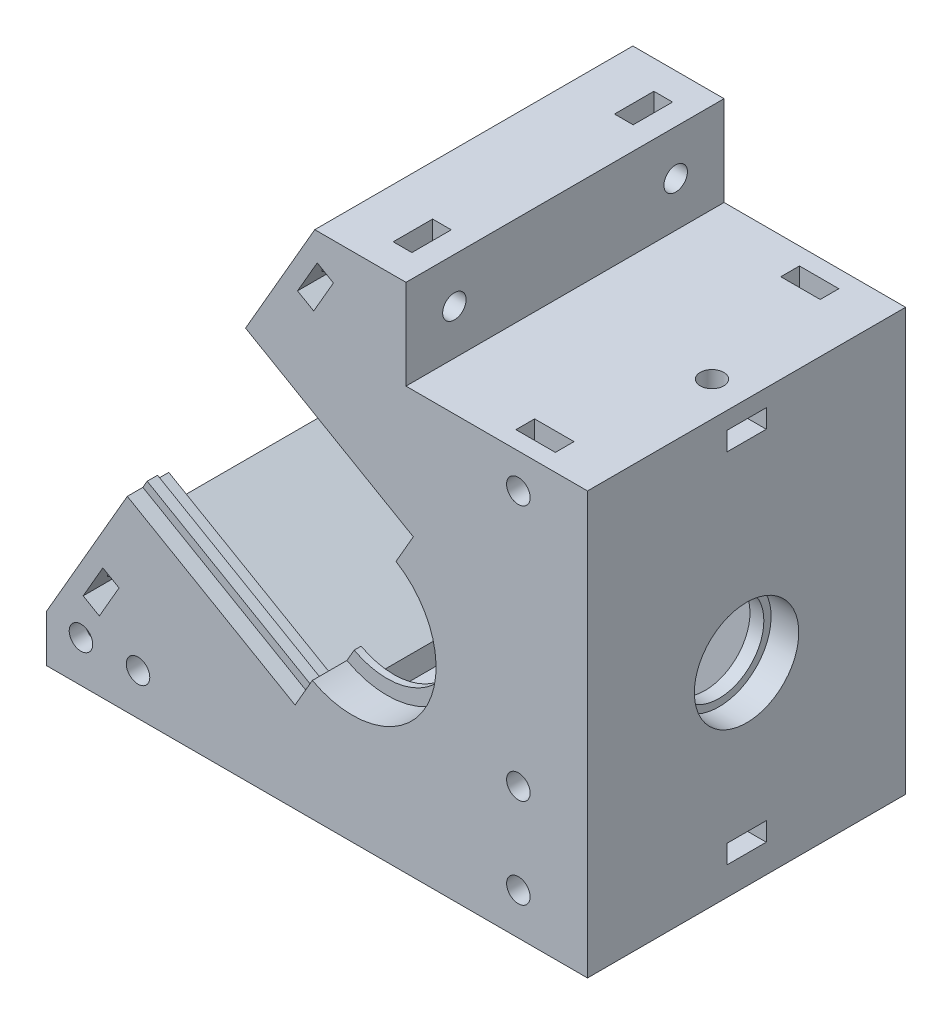
SolidWorks part; units mm, degrees
material "ABS"
ref_plane "Front Plane" through (0, 0, 0) normal (0, 0, 1) x (1, 0, 0)
ref_plane "Top Plane" through (0, 0, 0) normal (0, 1, 0) x (1, 0, 0)
ref_plane "Right Plane" through (0, 0, 0) normal (1, 0, 0) x (0, 0, -1)
sketch "Sketch1" plane through (0, 0, 0) normal (0, 0, 1) x (1, 0, 0)
  line L0 (-14, -24.2487) -> (-38, -10.3923)
  line L1 (-38, 33) -> (34, 33)
  line L2 (-38, 33) -> (-38, -31)
  line L3 (-38, -31) -> (34, -31)
  line L4 (34, 33) -> (34, -31)
  line L7 (-15, -31) -> (-15, -27.5)
  line L8 (-15, -27.5) -> (15, -27.5)
  line L9 (15, -27.5) -> (15, -31)
  line L16 (14, 24.2487) -> (-10, 38.1051)
  line L17 (7.75, 33) -> (7.75, 46)
  line L18 (7.75, 46) -> (-5.25, 46)
  line L19 (28, 10) -> (28, -10)
  line L20 (28, 10) -> (28, 14)
  line L21 (28, 14) -> (16.8, 22.4)
  line L22 (-38, -10.3923) -> (-5.4419, 46)
  line L23 (-5.4419, 46) -> (-5.25, 46)
  line L24 (-38, -10.3923) -> (-44.25, -21.2176)
  line L25 (-44.25, -21.2176) -> (-44.25, -31)
  line L26 (-44.25, -31) -> (-38, -31)
  line L27 (-44.25, -21.2176) -> (-44.25, -15.2176) construction
  line L28 (-44.25, -15.2176) -> (-8.906, 46) construction
  line L29 (-8.906, 46) -> (-5.4419, 46) construction
  line L30 (-10, 38.1051) -> (-12.5981, 39.6051) construction
  line L31 (-38, -10.3923) -> (-40.5981, -8.8923) construction
  line L32 (28, -10) -> (28, -14)
  line L33 (28, -14) -> (16.8, -22.4)
  circle A0 centre (0, 0) radius 28
  circle A1 centre (0, 0) radius 12.1
  circle A2 centre (0, 0) radius 10
  point P22 (28, 0)
  dimension "D1" = 56
  dimension "D2" = 24.2
  dimension "D3" = 20
  dimension "D4" = 34
  dimension "D6" = 3.5
  dimension "D7" = 15
  dimension "D8" = 15
  dimension "D10" = 38
  dimension "D5" = 33
  dimension "D9" = 31
  dimension "D11" = 30
  dimension "D12" = 7.75
  dimension "D13" = 13
  dimension "D14" = 13
  dimension "D15" = 20
  dimension "D16" = 9.1162
  dimension "D17" = 12.5
  dimension "D18" = 3
  dimension "D19" = 7.3038
  dimension "D20" = 7.3842
  dimension "D21" = 4
  dimension "D22" = 4
extrude "Boss-Extrude1" add sketch "Sketch1" along normal blind 6 contours A0 L20 L19 L8 L9 L3 L4 L1 L16 | A0 L0 L2 L3 L7 L8 | L25 L26 L2 L24 | L23 L22 L16 L1 L17 L18 | A0 L22 L0 | L22 A0 L8 A1 | A0 L16 L1 L22 | L22 L1 L16 | A0 L19 L20 | A0 L19 region at (-27.5845, -23.6186, 0) region at (-29.6112, -8.3492, 0) region at (-25.7125, -8.9071, 0) region at (-40.7539, -23.0811, 0) region at (-7.4692, 28.6958, 0) region at (11.6201, -26.2754, 0) region at (-8.035, 34.7017, 0) region at (25.6746, -12.8373, 0) region at (0.2743, 39.7035, 0) region at (25.6746, 12.8373, 0)
extrude "Boss-Extrude2" add sketch "Sketch1<3>" along normal blind 40 contours A0 L20 L19 L8 L9 L3 L4 L1 L16 | L23 L22 L16 L1 L17 L18 | A0 L0 L2 L3 L7 L8 | L25 L26 L2 L24 region at (-27.5845, -23.6186, 0) region at (-40.7539, -23.0811, 0) region at (11.6201, -26.2754, 0) region at (0.2743, 39.7035, 0)
sketch "Sketch1<3>" plane through (0, 0, 0) normal (0, 0, 1) x (1, 0, 0) same geometry as "Sketch1"
extrude "Boss-Extrude3" add sketch "Sketch1<4>" along normal blind 6 from surface contours A0 L20 L19 L8 L9 L3 L4 L1 L16 | L22 A0 L8 A1 | A0 L19 L20 | A0 L19 | A0 L0 L2 L3 L7 L8 | A0 L22 L0 | A0 L16 L1 L22 | L22 L1 L16 | L23 L22 L16 L1 L17 L18 | L25 L26 L2 L24 region at (-27.5845, -23.6186, 0) region at (-29.6112, -8.3492, 0) region at (-25.7125, -8.9071, 0) region at (-40.7539, -23.0811, 0) region at (-7.4692, 28.6958, 0) region at (11.6201, -26.2754, 0) region at (-8.035, 34.7017, 0) region at (25.6746, -12.8373, 0) region at (0.2743, 39.7035, 0) region at (25.6746, 12.8373, 0) starting at face at (14.8032, 7.3384, 40)
sketch "Sketch1<4>" plane through (0, 0, 0) normal (0, 0, 1) x (1, 0, 0) same geometry as "Sketch1"
extrude "Boss-Extrude4" add sketch "Sketch1<5>" against normal blind 1 from surface contours A1 A2 region at (-11.7578, 0, 0) starting at face at (4.1782, -2.8269, 6)
sketch "Sketch1<5>" plane through (0, 0, 0) normal (0, 0, 1) x (1, 0, 0) same geometry as "Sketch1"
extrude "Boss-Extrude5" add sketch "Sketch1<6>" along normal blind 1 from surface contours A1 A2 region at (-11.7578, 0, 0) starting at face at (4.1782, -2.8269, 40)
sketch "Sketch1<6>" plane through (0, 0, 0) normal (0, 0, 1) x (1, 0, 0) same geometry as "Sketch1"
sketch "Sketch2" plane through (0, -27.5, 0) normal (0, -1, 0) x (1, 0, 0)
  line L0 (15, 46) -> (15, 0) construction
  line L1 (15, 40) -> (-15, 40)
  line L2 (15, 40) -> (15, 6)
  line L3 (15, 6) -> (-15, 6)
  line L4 (-15, 40) -> (-15, 6)
  line L5 (-15, 46) -> (-15, 0) construction
  line L6 (-5.2678, 6) -> (5.2678, 6) construction
  line L7 (5.2678, 40) -> (-5.2678, 40) construction
sketch "Sketch3" plane through (0, 0, 0) normal (0, 0, -1) x (-1, 0, 0)
  line L0 (-6.05, 10.4789) -> (17.95, 24.3353)
  line L1 (44.25, -21.2176) -> (5.4419, 46) construction
  line L2 (6.05, -10.4789) -> (30.05, 3.3775)
  line L3 (-8.55, 14.809) -> (15.45, 28.6654)
  line L4 (8.2902, -14.959) -> (32.55, -0.9526)
  line L5 (6.05, -10.4789) -> (30.05, 3.3775) construction
  line L6 (-8.55, 14.809) -> (-6.05, 10.4789)
  line L7 (8.55, -14.809) -> (6.05, -10.4789)
  line L8 (-6.05, 10.4789) -> (6.05, -10.4789)
  line L9 (-8.55, 14.809) -> (-8.8098, 14.659)
  line L10 (-8.8098, 14.659) -> (8.2902, -14.959)
  line L11 (8.55, -14.809) -> (32.55, -0.9526) construction
  circle A0 centre (0, 0) radius 12.1 construction
  line M11 (44.25, -21.2176) -> (5.4419, 46)
  circle M17 centre (0, 0) radius 12.1
  dimension "D1" = 90
  dimension "D2" = 90
  dimension "D5" = 90
  dimension "D6" = 0.3
  dimension "D7" = 27.7128
  dimension "D3" = 5
  dimension "D4" = 5
extrude "Cut-Extrude1" cut sketch "Sketch2" against normal blind 10
extrude "Cut-Extrude2" cut sketch "Sketch3" against normal blind 49 contours L3 L6 L0 M11 | L2 L0 M17 M11 | L8 M17 | L9 L10 L6 M17 | L10 L8 M17 | L7 L4 L2 M11 | L10 L4 L7 M17 region at (-4.7, 19.5722, 0) region at (7.4296, 12.5684, 0) region at (-4.4474, 2.5677, 0) region at (-15.9416, 9.2039, 0) region at (0.1299, -0.075, 0) region at (-19.3, -5.7158, 0) region at (-7.1698, -12.7184, 0)
sketch "Sketch4" plane through (0.2598, -0.15, 0) normal (-0.866, 0.5, 0) x (0, 0, 1)
  line L0 (6, 17.1) -> (0, 17.1) construction
  line L1 (2.25, 17.1) -> (3.75, 17.1)
  line L2 (2.25, 17.1) -> (2.25, 15.85)
  line L3 (2.25, 15.85) -> (3.75, 15.85)
  line L4 (3.75, 17.1) -> (3.75, 15.85)
  line L5 (42.25, 17.1) -> (43.75, 17.1)
  line L6 (42.25, 17.1) -> (42.25, 15.85)
  line L7 (42.25, 15.85) -> (43.75, 15.85)
  line L8 (43.75, 17.1) -> (43.75, 15.85)
  line L9 (46, 17.1) -> (40, 17.1) construction
  line L10 (2.25, -15.85) -> (3.75, -15.85)
  line L11 (2.25, -15.85) -> (2.25, -17.1)
  line L12 (2.25, -17.1) -> (3.75, -17.1)
  line L13 (3.75, -15.85) -> (3.75, -17.1)
  line L14 (42.25, -15.85) -> (43.75, -15.85)
  line L15 (42.25, -15.85) -> (42.25, -17.1)
  line L16 (42.25, -17.1) -> (43.75, -17.1)
  line L17 (43.75, -15.85) -> (43.75, -17.1)
  line L18 (6, -17.1) -> (0, -17.1) construction
  line L19 (46, -17.1) -> (40, -17.1) construction
  point P6 (3, 17.1)
  point P7 (3, 17.1)
  point P12 (43, 17.1)
  point P15 (43, 17.1)
  point P28 (3, -17.1)
  point P29 (3, -17.1)
  point P30 (43, -17.1)
  point P33 (43, -17.1)
  dimension "D1" = 1.5
  dimension "D2" = 1.25
  dimension "D3" = 1.5
  dimension "D4" = 1.25
  dimension "D5" = 1.5
  dimension "D6" = 1.25
  dimension "D7" = 1.5
  dimension "D8" = 1.25
extrude "Boss-Extrude6" add sketch "Sketch4" along normal up to surface (28.0128 mm away) up to face at (-11.5855, 35.359, 23)
sketch "Sketch5" plane through (28, 0, 0) normal (-1, 0, 0) x (0, 0, 1)
  line L0 (40, 14) -> (6, -14) construction
  circle A0 centre (23, 0) radius 7.55
  circle A1 centre (23, 0) radius 6.5
  point P7 (23, 0)
  dimension "D1" = 15.1
  dimension "D2" = 13
extrude "Cut-Extrude3" cut sketch "Sketch5" against normal blind 49 contours A1 L0 | L0 A1 region at (28, -2.1295, 24.7537) region at (28, 2.1295, 21.2463)
extrude "Cut-Extrude4" cut sketch "Sketch5<3>" along normal blind 4 from surface contours L0 A0 A1 | A0 L0 A1 region at (28, 2.4881, 29.9351) region at (28, 4.6064, 28.3071) starting at face at (34, 6.5, 23)
sketch "Sketch5<3>" plane through (28, 0, 0) normal (-1, 0, 0) x (0, 0, 1) same geometry as "Sketch5"
sketch "Sketch6" plane through (-24, 13.8564, 0) normal (-0.866, 0.5, 0) x (0, 0, 1)
  line L0 (40, -28) -> (6, -28) construction
  line L1 (0, -40.5) -> (0, -17.1) construction
  line L2 (46, -17.1) -> (46, -40.5) construction
  line L3 (40, 28) -> (6, 28) construction
  line L5 (46, -40.5) -> (0, -40.5) construction
  circle A0 centre (4, -31) radius 1.7
  circle A1 centre (42, -31) radius 1.7
  circle A2 centre (42, 31) radius 1.7
  circle A3 centre (4, 31) radius 1.7
  dimension "D1" = 3.4
  dimension "D2" = 3.4
  dimension "D3" = 3.4
  dimension "D4" = 3.4
  dimension "D5" = 3
  dimension "D6" = 4
  dimension "D7" = 4
  dimension "D8" = 3
  dimension "D9" = 9.5
  dimension "D10" = 62
  dimension "D11" = 38
extrude "Cut-Extrude5" cut sketch "Sketch6" against normal blind 8
sketch "Sketch7" plane through (0, 0, 46) normal (0, 0, 1) x (1, 0, 0)
  line L0 (34, -31) -> (34, 33) construction
  line L1 (-44.25, -31) -> (34, -31)
  line L2 (-44.25, -31) -> (-44.25, -27)
  line L3 (-44.25, -27) -> (34, -27)
  line L4 (34, -31) -> (34, -27)
  line L6 (15, -27.5) -> (-15, -27.5) construction
  dimension "D1" = 0.5
extrude "Cut-Extrude6" cut sketch "Sketch7" against normal blind 64
sketch "Sketch8" plane through (0, 0, 46) normal (0, 0, 1) x (1, 0, 0)
  line L0 (34, -27) -> (-44.25, -27) construction
  line L1 (-44.25, -27) -> (-44.25, -21.2176) construction
  line L2 (34, -27) -> (34, 33) construction
  circle A0 centre (-39.25, -22) radius 1.7
  circle A1 centre (29, -22) radius 1.7
  dimension "D1" = 3.4
  dimension "D2" = 3.4
  dimension "D3" = 5
  dimension "D4" = 5
  dimension "D5" = 5
  dimension "D6" = 5
extrude "Cut-Extrude7" cut sketch "Sketch8" against normal blind 10 contours A0 region at (-39.25, -22, 46)
extrude "Cut-Extrude9" cut sketch "Sketch8<2>" along normal blind 10 from surface contours A0 region at (-39.25, -22, 46) starting at face at (-3.6295, 7.9996, 0)
sketch "Sketch8<2>" plane through (0, 0, 46) normal (0, 0, 1) x (1, 0, 0) same geometry as "Sketch8"
sketch "Sketch10" plane through (-44.25, 0, 0) normal (-1, 0, 0) x (0, 0, 1)
  line L0 (0, -27) -> (46, -27) construction
  line L1 (20.15, -21.2176) -> (25.85, -21.2176)
  line L2 (20.15, -21.2176) -> (20.15, -23.9176)
  line L3 (20.15, -23.9176) -> (25.85, -23.9176)
  line L4 (25.85, -21.2176) -> (25.85, -23.9176)
  line L5 (20.15, -21.2176) -> (25.85, -23.9176) construction
  line L6 (20.15, -23.9176) -> (25.85, -21.2176) construction
  line L7 (46, -21.2176) -> (0, -21.2176) construction
  point P0 (23, -22.5676)
  point P8 (23, -27)
  dimension "D1" = 5.7
  dimension "D2" = 2.7
extrude "Cut-Extrude10" cut sketch "Sketch10" against normal blind 8.5
sketch "Sketch11" plane through (34, 0, 0) normal (1, 0, 0) x (0, 0, -1)
  line L0 (0, -27) -> (-46, -27) construction
  line L1 (-43.7, -24.85) -> (-41, -24.85)
  line L2 (-43.7, -24.85) -> (-43.7, -19.15)
  line L3 (-43.7, -19.15) -> (-41, -19.15)
  line L4 (-41, -24.85) -> (-41, -19.15)
  line L5 (-43.7, -24.85) -> (-41, -19.15) construction
  line L6 (-43.7, -19.15) -> (-41, -24.85) construction
  line L7 (-46, -27) -> (-46, 33) construction
  line L8 (-5, -24.85) -> (-2.5, -24.85)
  line L9 (-5, -24.85) -> (-5, -19.15)
  line L10 (-5, -19.15) -> (-2.5, -19.15)
  line L11 (-2.5, -24.85) -> (-2.5, -19.15)
  line L12 (-5, -24.85) -> (-2.5, -19.15) construction
  line L13 (-5, -19.15) -> (-2.5, -24.85) construction
  line L14 (0, 33) -> (0, -27) construction
  point P0 (-42.35, -22)
  point P9 (-3.75, -22)
  dimension "D1" = 5.7
  dimension "D2" = 2.7
  dimension "D3" = 5
  dimension "D4" = 5
  dimension "D5" = 5.7
  dimension "D6" = 2.5
  dimension "D7" = 5
extrude "Cut-Extrude12" cut sketch "Sketch11" along normal blind 8.5 from surface starting at face at (-44.25, -23.3382, 23)
extrude "Cut-Extrude13" cut sketch "Sketch10<2>" along normal blind 8.5 from surface starting at face at (34, 3, 23)
sketch "Sketch10<2>" plane through (-44.25, 0, 0) normal (-1, 0, 0) x (0, 0, 1) same geometry as "Sketch10"
sketch "Sketch12" plane through (0, 0, 46) normal (0, 0, 1) x (1, 0, 0)
  line L0 (-36.0831, -11.6722) -> (-38.9331, -16.6086)
  line L1 (-38.9331, -16.6086) -> (-36.5949, -17.9586)
  line L2 (-36.5949, -17.9586) -> (-33.7449, -13.0222)
  line L3 (-33.7449, -13.0222) -> (-36.0831, -11.6722)
  line L4 (-32.55, -0.9526) -> (-44.25, -21.2176) construction
  line L6 (-39.5, -12.9904) -> (-28.0908, -19.5775) construction
  line L7 (-5.0831, 42.0214) -> (-7.9331, 37.085)
  line L8 (-7.9331, 37.085) -> (-5.5949, 35.735)
  line L9 (-5.5949, 35.735) -> (-2.7449, 40.6714)
  line L10 (-2.7449, 40.6714) -> (-5.0831, 42.0214)
  point P6 (-37.5081, -14.1404)
  point P7 (-39.5, -12.9904)
  point P17 (-8.7952, 39.4691)
  dimension "D1" = 2.7
  dimension "D2" = 5.7
  dimension "D3" = 5
  dimension "D4" = 9.5
  dimension "D5" = 90
  dimension "D6" = 2.7
  dimension "D7" = 5.7
  dimension "D8" = 62
extrude "Cut-Extrude14" cut sketch "Sketch12" against normal blind 7.5
extrude "Cut-Extrude15" cut sketch "Sketch12<2>" along normal blind 7.5 from surface starting at face at (-37.55, -22, 0)
sketch "Sketch12<2>" plane through (0, 0, 46) normal (0, 0, 1) x (1, 0, 0) same geometry as "Sketch12"
sketch "Sketch13" plane through (7.75, 0, 0) normal (1, 0, 0) x (0, 0, -1)
  line L0 (-46, 46) -> (0, 46) construction
  line L1 (-46, 46) -> (0, 33) construction
  circle A0 centre (-39, 39.5) radius 1.7
  circle A1 centre (-7, 39.5) radius 1.7
  point P10 (-23, 39.5)
  dimension "D1" = 3.4
  dimension "D2" = 3.4
  dimension "D3" = 6.5
  dimension "D4" = 16
  dimension "D5" = 16
extrude "Cut-Extrude16" cut sketch "Sketch13" against normal blind 10
sketch "Sketch14" plane through (0, 46, 0) normal (0, 1, 0) x (1, 0, 0)
  line L0 (1.75, -9.85) -> (4.45, -9.85)
  line L1 (1.75, -41.85) -> (4.45, -41.85)
  line L2 (1.75, -41.85) -> (1.75, -36.15)
  line L3 (1.75, -36.15) -> (4.45, -36.15)
  line L4 (4.45, -41.85) -> (4.45, -36.15)
  line L5 (1.75, -41.85) -> (4.45, -36.15) construction
  line L6 (1.75, -36.15) -> (4.45, -41.85) construction
  line L7 (1.75, -9.85) -> (1.75, -4.15)
  line L8 (1.75, -4.15) -> (4.45, -4.15)
  line L9 (4.45, -9.85) -> (4.45, -4.15)
  line L10 (1.75, -9.85) -> (4.45, -4.15) construction
  line L11 (1.75, -4.15) -> (4.45, -9.85) construction
  line L12 (7.75, -46) -> (7.75, 0) construction
  point P0 (3.1, -39)
  point P5 (3.1, -7)
  point P13 (7.75, -23)
  dimension "D1" = 2.7
  dimension "D2" = 5.7
  dimension "D3" = 2.7
  dimension "D4" = 5.7
  dimension "D5" = 6
  dimension "D6" = 16
  dimension "D7" = 16
extrude "Cut-Extrude17" cut sketch "Sketch14" against normal blind 10
sketch "Sketch15" plane through (0, 0, 46) normal (0, 0, 1) x (1, 0, 0)
  line L0 (0, 30.9475) -> (0, -37.7326) construction
  line L1 (0, 0) -> (-6.3411, -23.6652) construction
  line L2 (34, -27) -> (-44.25, -27) construction
  line L3 (0, 0) -> (6.3411, 23.6652) construction
  line L4 (34, 33) -> (7.75, 33) construction
  line L5 (-6.3411, -23.6652) -> (-16.7248, -20.8829) construction
  line L6 (-6.3411, -23.6652) -> (4.0426, -26.4475) construction
  line L7 (-16.7248, -20.8829) -> (-24.6937, -18.7476) construction
  line L8 (-24.6937, -18.7476) -> (-2.694, 63.3561) construction
  dimension "D1" = 15
  dimension "D2" = 24.5
  dimension "D3" = 44.25
  dimension "D4" = 34
  dimension "D5" = 27
  dimension "D6" = 15
  dimension "D7" = 24.5
  dimension "D8" = 1.4089
  dimension "D9" = 9.3348
  dimension "D10" = 40.3411
  dimension "D11" = 3.3348
  dimension "D12" = 10.75
  dimension "D13" = 10.75
  dimension "D14" = 8.25
  dimension "D15" = 85
  dimension "D16" = 17.3561
  dimension "D17" = 10.444
  dimension "D18" = 14.5802
sketch "Sketch17" plane through (0, 0, 46) normal (0, 0, 1) x (1, 0, 0)
  line L0 (34, -27) -> (-44.25, -27) construction
  circle A0 centre (-31, -22) radius 1.7
  circle A1 centre (24, -22) radius 1.7
  dimension "D2" = 3.4
  dimension "D3" = 3.4
  dimension "D1" = 5
  dimension "D4" = 31
  dimension "D5" = 24
extrude "Cut-Extrude19" cut sketch "Sketch17" against normal blind 20
extrude "Cut-Extrude20" cut sketch "Sketch17<2>" along normal blind 20 from surface starting at face at (-5.339, 38.8782, 0)
sketch "Sketch17<2>" plane through (0, 0, 46) normal (0, 0, 1) x (1, 0, 0) same geometry as "Sketch17"
sketch "Sketch19" plane through (0, -27, 0) normal (0, -1, 0) x (1, 0, 0)
  line L1 (-44.25, 46) -> (34, 46)
  line L2 (-44.25, 46) -> (-44.25, 0)
  line L3 (-44.25, 0) -> (34, 0)
  line L4 (34, 46) -> (34, 0)
extrude "Boss-Extrude7" add sketch "Sketch19" along normal blind 1
sketch "Sketch9" plane through (0, -28, 0) normal (0, -1, 0) x (1, 0, 0)
  line L1 (-44.25, 46) -> (34, 0) construction
  line L3 (-44.25, 46) -> (-44.25, 0) construction
  line L4 (34, 0) -> (34, 46) construction
  circle A0 centre (-39.25, 23) radius 1.7
  circle A1 centre (29, 23) radius 1.7
  point P10 (-5.125, 23)
  dimension "D1" = 3.4
  dimension "D2" = 3.4
  dimension "D3" = 5
  dimension "D4" = 5
  dimension "D5" = 68.25
extrude "Cut-Extrude8" cut sketch "Sketch9" against normal blind 10
sketch "Sketch20" plane through (34, 0, 0) normal (1, 0, 0) x (0, 0, -1)
  line L0 (0, -28) -> (-46, -28) construction
  circle A0 centre (-29, -13) radius 1.7
  circle A1 centre (-17, -13) radius 1.7
  circle A2 centre (-23, 0) radius 7.55 construction
  dimension "D1" = 3.4
  dimension "D2" = 3.4
  dimension "D3" = 15
  dimension "D4" = 6
  dimension "D5" = 12
sketch "Sketch22" plane through (0, -28, 0) normal (0, -1, 0) x (1, 0, 0)
  line L1 (26.85, 2.5) -> (21.15, 2.5)
  line L2 (26.85, 2.5) -> (26.85, 5.2)
  line L3 (26.85, 5.2) -> (21.15, 5.2)
  line L4 (21.15, 2.5) -> (21.15, 5.2)
  line L5 (26.85, 2.5) -> (21.15, 5.2) construction
  line L6 (26.85, 5.2) -> (21.15, 2.5) construction
  line L7 (34, 0) -> (34, 46) construction
  line L8 (-44.25, 0) -> (34, 0) construction
  line L12 (-28.15, 2.5) -> (-33.85, 2.5)
  line L13 (-28.15, 2.5) -> (-28.15, 5.2)
  line L14 (-28.15, 5.2) -> (-33.85, 5.2)
  line L15 (-33.85, 2.5) -> (-33.85, 5.2)
  line L16 (-28.15, 2.5) -> (-33.85, 5.2) construction
  line L17 (-28.15, 5.2) -> (-33.85, 2.5) construction
  line L18 (-28.15, 40.8) -> (-33.85, 40.8)
  line L19 (-28.15, 40.8) -> (-28.15, 43.5)
  line L20 (-28.15, 43.5) -> (-33.85, 43.5)
  line L21 (-33.85, 40.8) -> (-33.85, 43.5)
  line L22 (-28.15, 40.8) -> (-33.85, 43.5) construction
  line L23 (-28.15, 43.5) -> (-33.85, 40.8) construction
  line L24 (26.85, 40.8) -> (21.15, 40.8)
  line L25 (26.85, 40.8) -> (26.85, 43.5)
  line L26 (26.85, 43.5) -> (21.15, 43.5)
  line L27 (21.15, 40.8) -> (21.15, 43.5)
  line L28 (26.85, 40.8) -> (21.15, 43.5) construction
  line L29 (26.85, 43.5) -> (21.15, 40.8) construction
  line L30 (34, 46) -> (-44.25, 46) construction
  point P0 (24, 3.85)
  point P9 (-31, 3.85)
  point P14 (-31, 42.15)
  point P19 (24, 42.15)
  dimension "D3" = 2.7
  dimension "D4" = 5.7
  dimension "D1" = 10
  dimension "D2" = 2.5
  dimension "D5" = 2.7
  dimension "D6" = 5.7
  dimension "D7" = 2.7
  dimension "D8" = 5.7
  dimension "D9" = 2.7
  dimension "D10" = 5.7
  dimension "D11" = 55
  dimension "D12" = 2.5
extrude "Cut-Extrude22" cut sketch "Sketch22" against normal blind 9.5
sketch "Sketch23" plane through (0, 0, 46) normal (0, 0, 1) x (1, 0, 0)
  line L0 (34, -28) -> (34, 33) construction
  line L1 (34, 33) -> (7.75, 33) construction
  circle A0 centre (24, 28) radius 1.7
  circle A1 centre (24, -9) radius 1.7
  dimension "D1" = 3.4
  dimension "D4" = 3.4
  dimension "D2" = 10
  dimension "D3" = 5
  dimension "D5" = 37
sketch "Sketch24" plane through (0, 33, 0) normal (0, 1, 0) x (1, 0, 0)
  line L0 (34, -46) -> (7.75, -46) construction
  line L1 (21.15, -40.8) -> (26.85, -40.8)
  line L2 (21.15, -40.8) -> (21.15, -43.5)
  line L3 (21.15, -43.5) -> (26.85, -43.5)
  line L4 (26.85, -40.8) -> (26.85, -43.5)
  line L5 (21.15, -40.8) -> (26.85, -43.5) construction
  line L6 (21.15, -43.5) -> (26.85, -40.8) construction
  line L7 (34, -46) -> (34, 0) construction
  line L8 (21.15, -2.5) -> (26.85, -2.5)
  line L9 (21.15, -2.5) -> (21.15, -5.2)
  line L10 (21.15, -5.2) -> (26.85, -5.2)
  line L11 (26.85, -2.5) -> (26.85, -5.2)
  line L12 (21.15, -2.5) -> (26.85, -5.2) construction
  line L13 (21.15, -5.2) -> (26.85, -2.5) construction
  line L14 (7.75, 0) -> (34, 0) construction
  circle A0 centre (29, -23) radius 1.7
  point P0 (24, -42.15)
  point P9 (24, -3.85)
  point P19 (34, -23)
  dimension "D1" = 2.7
  dimension "D2" = 5.7
  dimension "D5" = 2.7
  dimension "D6" = 5.7
  dimension "D8" = 3.4
  dimension "D3" = 2.5
  dimension "D4" = 10
  dimension "D7" = 2.5
  dimension "D9" = 5
extrude "Cut-Extrude23" cut sketch "Sketch23" against normal blind 12
extrude "Cut-Extrude24" cut sketch "Sketch23<2>" along normal blind 12 from surface starting at face at (-29.3, -22, 0)
sketch "Sketch23<2>" plane through (0, 0, 46) normal (0, 0, 1) x (1, 0, 0) same geometry as "Sketch23"
extrude "Cut-Extrude25" cut sketch "Sketch24" against normal blind 8.5
sketch "Sketch26" plane through (34, 0, 0) normal (1, 0, 0) x (0, 0, -1)
  line L0 (-46, 33) -> (0, 33) construction
  line L1 (-25.85, 30.5) -> (-20.15, 30.5)
  line L2 (-25.85, 30.5) -> (-25.85, 27.8)
  line L3 (-25.85, 27.8) -> (-20.15, 27.8)
  line L4 (-20.15, 30.5) -> (-20.15, 27.8)
  line L5 (-25.85, 30.5) -> (-20.15, 27.8) construction
  line L6 (-25.85, 27.8) -> (-20.15, 30.5) construction
  point P0 (-23, 29.15)
  point P8 (-23, 33)
  dimension "D1" = 5.7
  dimension "D2" = 2.7
  dimension "D3" = 2.5
extrude "Cut-Extrude27" cut sketch "Sketch26" against normal blind 8.5
sketch "Sketch27" plane through (0, 0, 6) normal (0, 0, 1) x (1, 0, 0)
  line L1 (24, -12.2909) -> (26.85, -10.6454)
  line L2 (26.85, -10.6454) -> (26.85, -7.3546)
  line L3 (26.85, -7.3546) -> (24, -5.7091)
  line L4 (24, -5.7091) -> (21.15, -7.3546)
  line L5 (21.15, -7.3546) -> (21.15, -10.6454)
  line L6 (21.15, -10.6454) -> (24, -12.2909)
  circle A0 centre (24, -9) radius 2.85 construction
  dimension "D1" = 5.7
extrude "Cut-Extrude28" cut sketch "Sketch27" against normal blind 3
extrude "Cut-Extrude29" cut sketch "Sketch27<2>" along normal blind 3 from surface starting at face at (25.7, -9, 40)
sketch "Sketch27<2>" plane through (0, 0, 6) normal (0, 0, 1) x (1, 0, 0) same geometry as "Sketch27"
sketch "Sketch28" plane through (34, 0, 0) normal (1, 0, 0) x (0, 0, -1)
  circle A0 centre (-23, 0) radius 18 construction
  dimension "D1" = 36
sketch "Sketch29" plane through (34, 0, 0) normal (1, 0, 0) x (0, 0, -1)
  circle A0 centre (-39, 28) radius 1.65
  circle A1 centre (-7, 28) radius 1.65
  circle A2 centre (-42, -23) radius 1.65
  circle A3 centre (-4, -23) radius 1.65
  dimension "D1" = 3.3
  dimension "D2" = 16
  dimension "D3" = 16
  dimension "D4" = 28
  dimension "D5" = 23
  dimension "D6" = 19
  dimension "D7" = 19
extrude "Cut-Extrude30" [suppressed] cut sketch "Sketch29" against normal blind 15
sketch "Sketch30" plane through (0, 33, 0) normal (0, 1, 0) x (1, 0, 0)
  line L0 (34, -46) -> (34, 0) construction
  line L1 (29.3, -9.85) -> (32, -9.85)
  line L2 (29.3, -9.85) -> (29.3, -4.15)
  line L3 (29.3, -4.15) -> (32, -4.15)
  line L4 (32, -9.85) -> (32, -4.15)
  line L5 (29.3, -9.85) -> (32, -4.15) construction
  line L6 (29.3, -4.15) -> (32, -9.85) construction
  line L7 (29.3, -41.85) -> (32, -41.85)
  line L8 (29.3, -41.85) -> (29.3, -36.15)
  line L9 (29.3, -36.15) -> (32, -36.15)
  line L10 (32, -41.85) -> (32, -36.15)
  line L11 (29.3, -41.85) -> (32, -36.15) construction
  line L12 (29.3, -36.15) -> (32, -41.85) construction
  point P0 (30.65, -7)
  point P5 (30.65, -39)
  point P12 (34, -23)
  dimension "D1" = 2.7
  dimension "D2" = 5.7
  dimension "D3" = 2.7
  dimension "D4" = 5.7
  dimension "D5" = 16
  dimension "D6" = 16
  dimension "D7" = 2
extrude "Cut-Extrude31" [suppressed] cut sketch "Sketch30" against normal blind 8.5
sketch "Sketch31" plane through (0, -28, 0) normal (0, -1, 0) x (1, 0, 0)
  line L0 (34, 0) -> (34, 46) construction
  line L1 (32, 44.85) -> (29.3, 44.85)
  line L2 (32, 44.85) -> (32, 39.15)
  line L3 (32, 39.15) -> (29.3, 39.15)
  line L4 (29.3, 44.85) -> (29.3, 39.15)
  line L5 (32, 44.85) -> (29.3, 39.15) construction
  line L6 (32, 39.15) -> (29.3, 44.85) construction
  line L7 (32, 6.85) -> (29.3, 6.85)
  line L8 (32, 6.85) -> (32, 1.15)
  line L9 (32, 1.15) -> (29.3, 1.15)
  line L10 (29.3, 6.85) -> (29.3, 1.15)
  line L11 (32, 6.85) -> (29.3, 1.15) construction
  line L12 (32, 1.15) -> (29.3, 6.85) construction
  point P0 (30.65, 42)
  point P5 (30.65, 4)
  point P13 (34, 23)
  dimension "D1" = 2
  dimension "D2" = 2.7
  dimension "D3" = 5.7
  dimension "D4" = 5.7
  dimension "D5" = 19
  dimension "D6" = 19
  dimension "D7" = 2.7
extrude "Cut-Extrude32" [suppressed] cut sketch "Sketch31" against normal blind 8.5
equation "\"D8@Sketch1\"=\"D7@Sketch1\""
equation "\"D4@Sketch4\"=\"D2@Sketch4\""
equation "\"D6@Sketch4\"=\"D2@Sketch4\""
equation "\"D8@Sketch4\"=\"D2@Sketch4\""
equation "\"D4@Sketch6\"=\"D3@Sketch6\""
equation "\"D2@Sketch6\"=\"D3@Sketch6\""
equation "\"D1@Sketch6\"=\"D3@Sketch6\""
equation "\"D2@Sketch13\"=\"D1@Sketch13\""
equation "\"D5@Sketch13\"=\"D4@Sketch13\""
equation "\"D3@Sketch17\"=\"D2@Sketch17\""
equation "\"D2@Sketch8\"=\"D1@Sketch8\""
equation "\"D1@Sketch14\"=\"D3@Sketch14\""
equation "\"D1@Sketch20\"=\"D2@Sketch20\""
equation "\"D9@Sketch22\"=\"D3@Sketch22\""
equation "\"D5@Sketch22\"=\"D3@Sketch22\""
equation "\"D7@Sketch22\"=\"D3@Sketch22\""
equation "\"D5@Sketch24\"=\"D1@Sketch24\""
